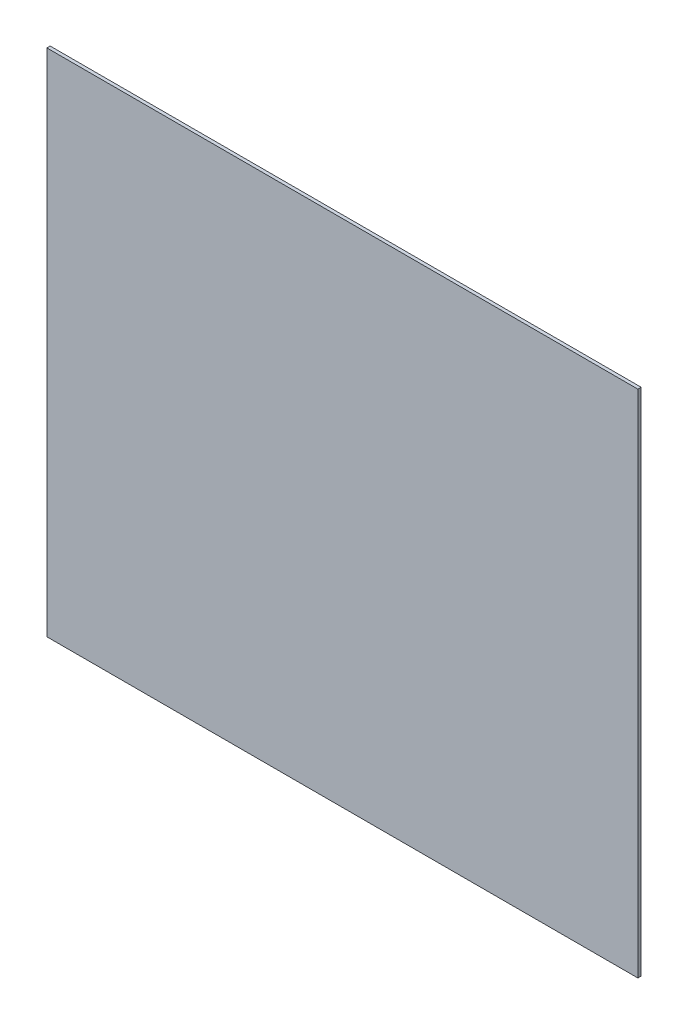
SolidWorks part; units mm, degrees
ref_plane "Plan de face" through (0, 0, 0) normal (0, 0, 1) x (1, 0, 0)
ref_plane "Plan de dessus" through (0, 0, 0) normal (0, 1, 0) x (1, 0, 0)
ref_plane "Plan de droite" through (0, 0, 0) normal (1, 0, 0) x (0, 0, -1)
sketch "Esquisse1" plane through (0, 0, 0) normal (0, 0, 1) x (1, 0, 0)
  line L1 (-67.1197, 30.2525) -> (472.8803, 30.2525)
  line L2 (-67.1197, 30.2525) -> (-67.1197, -435.7475)
  line L3 (-67.1197, -435.7475) -> (472.8803, -435.7475)
  line L4 (472.8803, 30.2525) -> (472.8803, -435.7475)
  dimension "D1" = 540
  dimension "D2" = 466
extrude "Boss.-Extru.1" add sketch "Esquisse1" along normal blind 3
equation "\"EpaisseurPlaque\"= 3"
equation "\"D1@Boss.-Extru.1\"=\"EpaisseurPlaque\""
equation "\"ProfondeurBoite\"=460"
equation "\"LongueurSyphon\"=170"
equation "\"LargeurSyphon\"=120"
equation "\"HauteurCoteDroit\"= 490"
equation "\"HauteurCoteGauche\"= 540"
equation "\"HauteurSolSyphon\"= 300"
equation "\"HauteurSyphon\"=\"HauteurCoteGauche\"-\"HauteurSolSyphon\""
equation "\"LargeurBoite\"= \"LargeurDroite\" + \"LargeurGauche\" + \"LargeurSyphon\""
equation "\"D2@Esquisse1\"=\"ProfondeurBoite\" + 2 *\"EpaisseurPlaque\""
equation "\"D1@Esquisse1\"=\"HauteurCoteGauche\" "
equation "\"LargeurDroite\"=10"
equation "\"LargeurGauche\"=150"
